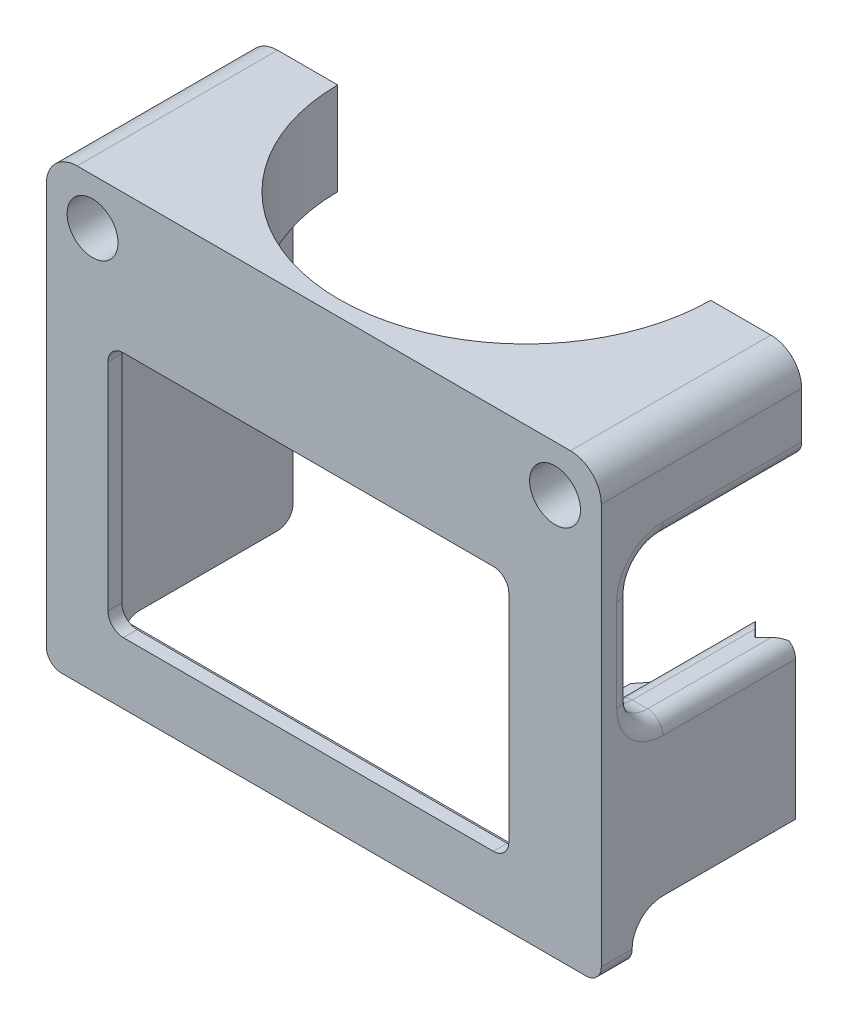
SolidWorks part; units mm, degrees
ref_plane "Front Plane" through (0, 0, 0) normal (0, 0, 1) x (1, 0, 0)
ref_plane "Top Plane" through (0, 0, 0) normal (0, 1, 0) x (1, 0, 0)
ref_plane "Right Plane" through (0, 0, 0) normal (1, 0, 0) x (0, 0, -1)
sketch "Sketch1" plane through (0, 0, 0) normal (0, 1, 0) x (1, 0, 0)
  line L0 (0, 0) -> (36, 0)
  line L1 (36, 0) -> (36, 13)
  line L2 (36, 13) -> (30.0996, 13)
  line L3 (0, 0) -> (0, 13)
  line L4 (0, 13) -> (5.9004, 13)
  arc A0 (30.0996, 13) -> (5.9004, 13) centre (18, 13.1) cw
  dimension "D1" = 12.1
  dimension "D2" = 13
  dimension "D3" = 36
  dimension "D4" = 18
  dimension "D5" = 13.1
  dimension "D6" = 13
extrude "Boss-Extrude1" add sketch "Sketch1" along normal blind 6
sketch "Sketch2" plane through (0, 0, 0) normal (0, -1, 0) x (1, 0, 0)
  line L0 (36, 0) -> (0, 0)
  line L1 (0, 0) -> (0, -13)
  line L2 (0, -13) -> (3, -13)
  line L3 (5.9004, -13) -> (0, -13) construction
  line L4 (3, -13) -> (3, -0.9)
  line L5 (3, -0.9) -> (33, -0.9)
  line L6 (33, -0.9) -> (33, -2)
  line L8 (33, -2) -> (36, -2)
  line L9 (36, 0) -> (36, -13) construction
  line L10 (36, -2) -> (36, 0)
  dimension "D1" = 0.9
  dimension "D2" = 3
  dimension "D3" = 3
  dimension "D4" = 2
extrude "Boss-Extrude2" add sketch "Sketch2" along normal blind 20
sketch "Sketch3" plane through (0, 0, 0) normal (0, 0, 1) x (1, 0, 0)
  line L0 (0, 6) -> (36, 6) construction
  line L1 (0, 6) -> (0, -20) construction
  line L2 (36, 6) -> (36, -20) construction
  circle A0 centre (3, 3) radius 1.65
  circle A1 centre (33, 3) radius 1.65
  dimension "D3" = 3.3
  dimension "D4" = 3.3
  dimension "D1" = 3
  dimension "D2" = 3
  dimension "D5" = 3
extrude "Cut-Extrude1" cut sketch "Sketch3" against normal through all
sketch "Sketch4" plane through (0, -20, 0) normal (0, -1, 0) x (1, 0, 0)
  line L1 (36, -2) -> (0, -2)
  line L2 (36, -2) -> (36, 0)
  line L3 (36, 0) -> (0, 0)
  line L4 (0, -2) -> (0, 0)
extrude "Boss-Extrude3" add sketch "Sketch4" along normal blind 3
sketch "Sketch5" plane through (0, 0, 0) normal (0, 0, 1) x (1, 0, 0)
  line L0 (0, 6) -> (36, 6) construction
  line L1 (30, -3) -> (4, -3)
  line L2 (30, -3) -> (30, -19)
  line L3 (30, -19) -> (4, -19)
  line L4 (4, -3) -> (4, -19)
  line L5 (36, 6) -> (36, -23) construction
  line L6 (0, 6) -> (0, -23) construction
  dimension "D1" = 9
  dimension "D2" = 16
  dimension "D3" = 6
  dimension "D4" = 4
extrude "Cut-Extrude2" cut sketch "Sketch5" against normal blind 3
sketch "Sketch6" plane through (0, 0, -2) normal (0, 0, -1) x (-1, 0, 0)
  line L0 (-33, -20) -> (-33, 0) construction
  line L1 (-33, -10) -> (-36, -10)
  line L2 (-33, -10) -> (-33, -20)
  line L3 (-33, -20) -> (-36, -20)
  line L4 (-36, -10) -> (-36, -20)
  line L5 (-36, -23) -> (-36, 0) construction
  dimension "D1" = 10
extrude "Boss-Extrude4" add sketch "Sketch6" along normal blind 11
fillet "Fillet1" radius 2 3 edges at (34.5, -10, -2) (34.5, 0, -2) (34.5, -20, -2)
sketch "Sketch7" plane through (0, -20, 0) normal (0, -1, 0) x (1, 0, 0)
  line L0 (36, -13) -> (34.4582, -11.5)
  line L1 (34.4582, -11.5) -> (33, -13)
  line L2 (36, -13) -> (33, -13)
  dimension "D1" = 1.5
extrude "Cut-Extrude3" cut sketch "Sketch7" against normal blind 10
chamfer "Chamfer1" distance 0.4 angle 90 2 edges at (33, -15, -13) (36, -15, -13) first distance on face at (33, -11.9623, -4.2325) first distance on face at (36, -9.6604, -5.4429)
fillet "Fillet3" radius 2 4 edges at (33, 0, -2.45) (3, 0, -6.95) (0, 6, -6.5) (36, 6, -6.5)
fillet "Fillet4" radius 1 4 edges at (36, -23, -1) (0, -23, -1) (1.5, -20, -13) (1.5, -20, -2)
fillet "Fillet5" radius 1 9 edges at (33, -10, -8.3) (33, -9.4142, -2.5858) (32.4142, -0.5858, -2.5858) (36, -10, -8.3) (36, -9.4142, -2.5858) (36, 0, -8.5) (36, -0.5858, -2.5858) (33, -5, -2) (36, -5, -2)
fillet "Fillet6" radius 1 4 edges at (4, -19, -0.45) (30, -19, -0.45) (4, -3, -0.45) (30, -3, -0.45)
ref_plane "Plane1" through (33, -20, -0.9) normal (0, 1, 0) x (1, 0, 0)
sketch "Sketch9" plane through (0, 0, -0.9) normal (0, 0, -1) x (-1, 0, 0)
  line L1 (-33, -20) -> (-31, -20)
  line L2 (-33, -20) -> (-33, -12.0265)
  line L3 (-33, -12.0265) -> (-31, -12.0265)
  line L4 (-31, -20) -> (-31, -12.0265)
  dimension "D1" = 2
extrude "Boss-Extrude5" add sketch "Sketch9" along normal blind 6
fillet "Fillet7" radius 8 1 edges at (33, -16.0133, -6.9)
fillet "Fillet8" radius 0.8 3 edges at (31, -16.0133, -0.9) (33, -20, -3) (33, -12.0265, -6.5458)
